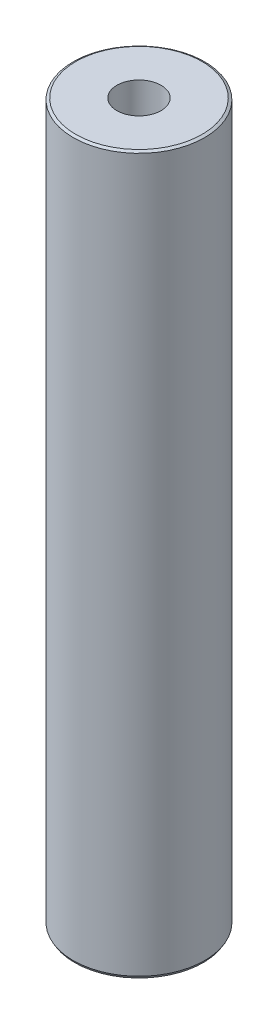
SolidWorks part; units mm, degrees
ref_plane "Front Plane" through (0, 0, 0) normal (0, 0, 1) x (1, 0, 0)
ref_plane "Top Plane" through (0, 0, 0) normal (0, 1, 0) x (1, 0, 0)
ref_plane "Right Plane" through (0, 0, 0) normal (1, 0, 0) x (0, 0, -1)
sketch "Sketch1" plane through (0, 0, 0) normal (0, 1, 0) x (1, 0, 0)
  circle A0 centre (0, 0) radius 47.5
  dimension "SHAFT_OD" = 95
extrude "Boss-Extrude1" add sketch "Sketch1" along normal blind 517.92
sketch "Sketch2" plane through (0, 0, 0) normal (0, 1, 0) x (1, 0, 0)
  circle A0 centre (0, 0) radius 15.945
  dimension "BORE_D" = 31.89
extrude "Cut-Extrude1" cut sketch "Sketch2" along normal through all
chamfer "Chamfer1" distance 1.0736 angle 60 2 edges at (0, 517.92, 47.5) (0, 0, 47.5) first distance on face at (0, 517.92, 47.5) first distance on face at (0, 0, 15.945)
